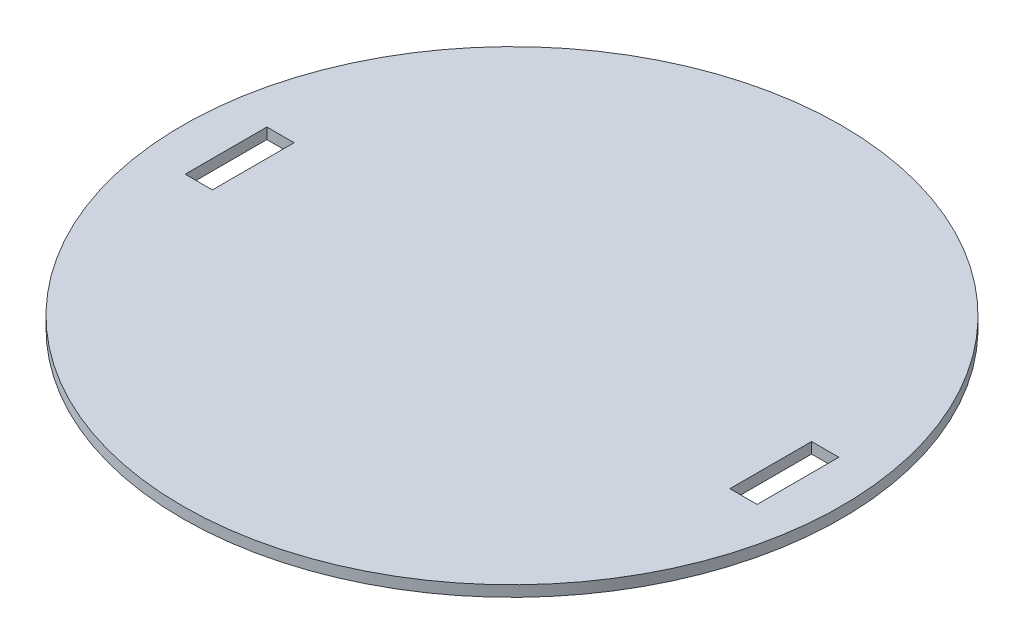
SolidWorks part; units mm, degrees
ref_plane "Front Plane" through (0, 0, 0) normal (0, 0, 1) x (1, 0, 0)
ref_plane "Top Plane" through (0, 0, 0) normal (0, 1, 0) x (1, 0, 0)
ref_plane "Right Plane" through (0, 0, 0) normal (1, 0, 0) x (0, 0, -1)
sketch "Bottom" plane through (0, 0, 0) normal (0, 1, 0) x (-1, 0, 0)
  line L0 (0, 0) -> (100, 0) construction
  line L1 (0, 2.2) -> (0, -2.2) construction
  line L2 (105, -15) -> (95, -15)
  line L3 (105, -15) -> (105, 15)
  line L4 (105, 15) -> (95, 15)
  line L5 (95, -15) -> (95, 15)
  line L6 (105, -15) -> (95, 15) construction
  line L7 (105, 15) -> (95, -15) construction
  line L8 (-105, 15) -> (-95, 15)
  line L9 (-95, -15) -> (-95, 15)
  line L10 (-105, -15) -> (-95, -15)
  line L11 (-105, -15) -> (-105, 15)
  line L12 (-105, 15) -> (-95, -15) construction
  line L13 (-105, -15) -> (-95, 15) construction
  circle A0 centre (0, 0) radius 121
  point P8 (0, 0)
  dimension "D1" = 242
  dimension "D2" = 100
  dimension "D3" = 30
  dimension "D4" = 10
extrude "Bottom-Extrude" add sketch "Bottom" along normal blind 4
equation "\"inner radius\"= 230"
equation "\"wall thickness\"= 6 "
equation "\"outer radius\"= \"inner radius\" + 2 * \"wall thickness\""
equation "\"height\" = 40"
equation "\"D1@Bottom\"=\"outer radius\""
equation "\"wheel distance\" = 100"
equation "\"D2@Bottom\"=\"wheel distance\""
equation "\"screw length\" = 15"
equation "\"top bottom thickness\" = 4"
equation "\"D1@Bottom-Extrude\"=\"top bottom thickness\""
equation "\"accel distance\" = 75"
equation "\"tolerance\" = 0.3"
equation "\"wheel hole width\" = 30"
equation "\"D3@Bottom\"=\"wheel hole width\""
